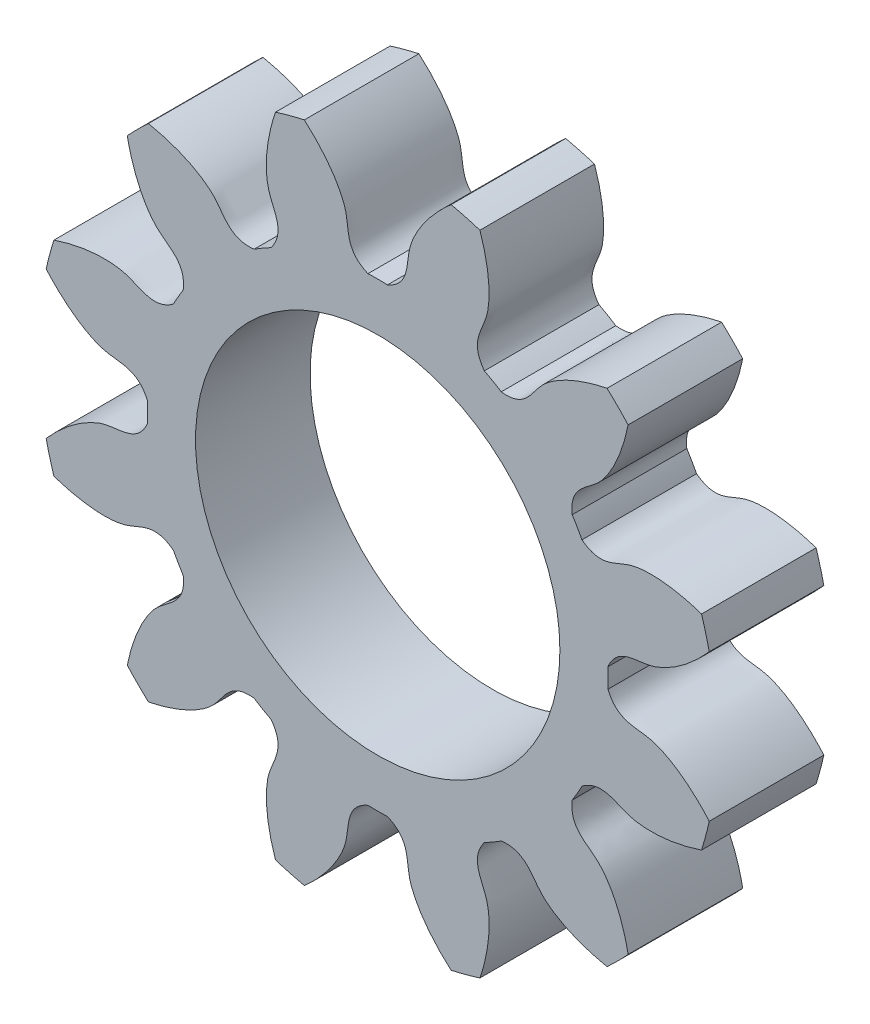
SolidWorks part; units mm, degrees
material "黄铜"
ref_plane "前视基准面" through (0, 0, 0) normal (0, 0, 1) x (1, 0, 0)
ref_plane "上视基准面" through (0, 0, 0) normal (0, 1, 0) x (1, 0, 0)
ref_plane "右视基准面" through (0, 0, 0) normal (1, 0, 0) x (0, 0, -1)
sketch "草图1" plane through (0, 0, 0) normal (0, 0, 1) x (1, 0, 0)
  circle A0 centre (0, 0) radius 11.8533
extrude "凸台-拉伸1" add sketch "草图1" along normal blind 4
ref_axis "基准轴1" through (0, 0, -0.2) along (0, 0, 1)
sketch "草图2" plane through (0, 0, 0) normal (0, 0, 1) x (1, 0, 0)
  line L0 (0, 0) -> (0, 11.8533) construction
  circle A0 centre (0, 0) radius 11.8533 construction
  arc A1 (0.3401, 8.0361) -> (-0.3401, 8.0361) centre (0, 0) ccw
  arc A2 (5.9226, 13.3688) -> (-5.9226, 13.3688) centre (0, 0) ccw
  spline S0 degree 3 poles (0.3401, 8.0361) (1.1528, 8.3808) (0.9726, 9.0506) (1.145, 9.6342) (1.1559, 9.6688) (1.1688, 9.7068) (1.1837, 9.7481) (1.2008, 9.7926) (1.2203, 9.8404) (1.2422, 9.8912) (1.2667, 9.9451) (1.2939, 10.002) (1.324, 10.0616) (1.357, 10.1241) (1.3932, 10.1892) (1.4325, 10.2569) (1.4752, 10.327) (1.5213, 10.3995) (1.571, 10.4743) (1.6243, 10.5512) (1.6814, 10.6301) (1.7424, 10.7108) (1.8073, 10.7934) (1.8763, 10.8776) (1.9495, 10.9633) (2.0268, 11.0503) (2.1085, 11.1386) (2.1946, 11.228) (2.2852, 11.3184) (2.3803, 11.4096) (2.48, 11.5014) (2.5844, 11.5938) (2.6936, 11.6865) (2.8075, 11.7795) (2.9263, 11.8725) (3.05, 11.9654) (3.1786, 12.058) (3.3121, 12.1502) (3.4507, 12.2419) (3.5943, 12.3328) (3.7429, 12.4228) (3.8967, 12.5117) (4.0555, 12.5993) (4.2194, 12.6856) (4.3885, 12.7702) (4.5626, 12.8531) (4.7418, 12.9341) (4.9262, 13.013) (5.1156, 13.0896) (5.3101, 13.1638) (5.5785, 13.26) (5.7837, 13.3267) (5.9226, 13.3688) knots 0 0 0 0 0.218015 0.222044 0.226546 0.231522 0.236972 0.242897 0.249295 0.256167 0.263513 0.271332 0.279626 0.288394 0.297636 0.307351 0.317541 0.328204 0.339341 0.350953 0.363038 0.375597 0.38863 0.402137 0.416118 0.430573 0.445502 0.460904 0.476781 0.493132 0.509956 0.527255 0.545027 0.563273 0.581994 0.601188 0.620856 0.640998 0.661614 0.682704 0.704268 0.726305 0.748817 0.771803 0.795262 0.819196 0.843603 0.868484 0.89384 0.919669 0.945972 1 1 1 1
  spline S1 degree 3 poles (-0.3401, 8.0361) (-1.1528, 8.3808) (-0.9726, 9.0506) (-1.145, 9.6342) (-1.1559, 9.6688) (-1.1688, 9.7068) (-1.1837, 9.7481) (-1.2008, 9.7926) (-1.2203, 9.8404) (-1.2422, 9.8912) (-1.2667, 9.9451) (-1.2939, 10.002) (-1.324, 10.0616) (-1.357, 10.1241) (-1.3932, 10.1892) (-1.4325, 10.2569) (-1.4752, 10.327) (-1.5213, 10.3995) (-1.571, 10.4743) (-1.6243, 10.5512) (-1.6814, 10.6301) (-1.7424, 10.7108) (-1.8073, 10.7934) (-1.8763, 10.8776) (-1.9495, 10.9633) (-2.0268, 11.0503) (-2.1085, 11.1386) (-2.1946, 11.228) (-2.2852, 11.3184) (-2.3803, 11.4096) (-2.48, 11.5014) (-2.5844, 11.5938) (-2.6936, 11.6865) (-2.8075, 11.7795) (-2.9263, 11.8725) (-3.05, 11.9654) (-3.1786, 12.058) (-3.3121, 12.1502) (-3.4507, 12.2419) (-3.5943, 12.3328) (-3.7429, 12.4228) (-3.8967, 12.5117) (-4.0555, 12.5993) (-4.2194, 12.6856) (-4.3885, 12.7702) (-4.5626, 12.8531) (-4.7418, 12.9341) (-4.9262, 13.013) (-5.1156, 13.0896) (-5.3101, 13.1638) (-5.5785, 13.26) (-5.7837, 13.3267) (-5.9226, 13.3688) knots 0 0 0 0 0.218015 0.222044 0.226546 0.231522 0.236972 0.242897 0.249295 0.256167 0.263513 0.271332 0.279626 0.288394 0.297636 0.307351 0.317541 0.328204 0.339341 0.350953 0.363038 0.375597 0.38863 0.402137 0.416118 0.430573 0.445502 0.460904 0.476781 0.493132 0.509956 0.527255 0.545027 0.563273 0.581994 0.601188 0.620856 0.640998 0.661614 0.682704 0.704268 0.726305 0.748817 0.771803 0.795262 0.819196 0.843603 0.868484 0.89384 0.919669 0.945972 1 1 1 1
extrude "切除-拉伸1" cut sketch "草图2" along normal through all
pattern_circular "阵列(圆周)1" count 12 every 30 about axis through (0, 0, -0.2) along (0, 0, 1) of "切除-拉伸1"
sketch "草图3" plane through (0, 0, 0) normal (0, 0, 1) x (1, 0, 0)
  circle A0 centre (0, 0) radius 10.16 construction
  dimension "Dn" = 20.32
sketch "草图4" plane through (0, 0, 4) normal (0, 0, 1) x (1, 0, 0)
  circle A0 centre (0, 0) radius 6.36
  dimension "D1" = 12.72
extrude "切除-拉伸2" cut sketch "草图4" against normal blind 10
